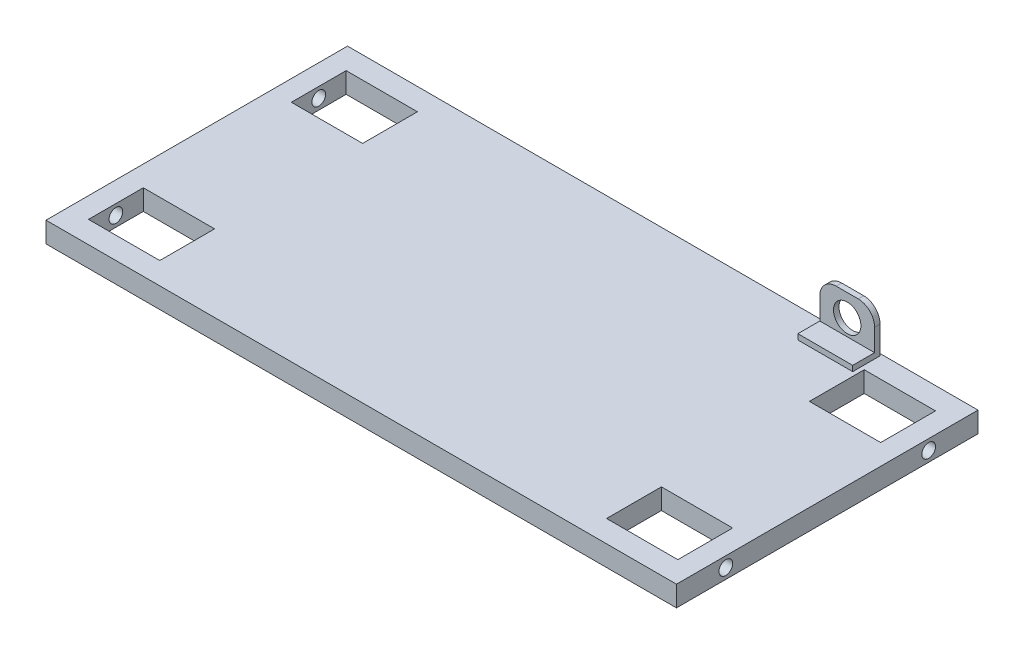
SolidWorks part; units mm, degrees
ref_plane "前视基准面" through (0, 0, 0) normal (0, 0, 1) x (1, 0, 0)
ref_plane "上视基准面" through (0, 0, 0) normal (0, 1, 0) x (1, 0, 0)
ref_plane "右视基准面" through (0, 0, 0) normal (1, 0, 0) x (0, 0, -1)
sketch "Sketch1" plane through (0, 0, 0) normal (0, 1, 0) x (1, 0, 0)
  line L1 (146.05, -69.85) -> (-146.05, -69.85)
  line L2 (146.05, -69.85) -> (146.05, 69.85)
  line L3 (146.05, 69.85) -> (-146.05, 69.85)
  line L4 (-146.05, -69.85) -> (-146.05, 69.85)
  line L5 (146.05, -69.85) -> (-146.05, 69.85) construction
  line L6 (146.05, 69.85) -> (-146.05, -69.85) construction
  point P1 (0, 0)
  dimension "D1" = 139.7
  dimension "D2" = 292.1
extrude "Boss-Extrude1" add sketch "Sketch1" along normal blind 9.525
sketch "Sketch2" plane through (0, 9.525, 0) normal (0, 1, 0) x (1, 0, 0)
  line L0 (-146.05, 0) -> (146.05, 0) construction
  line L1 (-146.05, 69.85) -> (-146.05, -69.85) construction
  line L2 (146.05, -69.85) -> (146.05, 69.85) construction
  line L3 (0, 69.85) -> (0, -69.85) construction
  line L4 (146.05, 69.85) -> (-146.05, 69.85) construction
  line L5 (-146.05, -69.85) -> (146.05, -69.85) construction
  line L6 (-136.525, 34.29) -> (-103.505, 34.29)
  line L7 (-103.505, -59.69) -> (-136.525, -59.69)
  line L8 (-103.505, -59.69) -> (-103.505, -34.29)
  line L9 (-103.505, 59.69) -> (-136.525, 59.69)
  line L10 (-136.525, -59.69) -> (-136.525, -34.29)
  line L11 (-103.505, -59.69) -> (-136.525, 59.69) construction
  line L12 (-103.505, 59.69) -> (-136.525, -59.69) construction
  line L13 (-136.525, -34.29) -> (-103.505, -34.29)
  line L14 (-103.505, 34.29) -> (-103.505, 59.69)
  line L15 (-136.525, 34.29) -> (-136.525, 59.69)
  line L16 (103.505, 34.29) -> (103.505, 59.69)
  line L17 (136.525, 34.29) -> (103.505, 34.29)
  line L18 (136.525, 34.29) -> (136.525, 59.69)
  line L19 (103.505, 59.69) -> (136.525, 59.69)
  line L20 (103.505, -59.69) -> (136.525, -59.69)
  line L21 (103.505, -59.69) -> (103.505, -34.29)
  line L22 (136.525, -59.69) -> (136.525, -34.29)
  line L23 (136.525, -34.29) -> (103.505, -34.29)
  point P12 (-120.015, 0)
  dimension "D1" = 10.16
  dimension "D2" = 33.02
  dimension "D3" = 25.4
  dimension "D4" = 9.525
extrude "Cut-Extrude1" cut sketch "Sketch2" against normal up to surface (9.525 mm away) up to face at (0, 0, 0)
sketch "Sketch3" plane through (146.05, 0, 0) normal (1, 0, 0) x (0, 0, -1)
  line L0 (-69.85, 4.7625) -> (69.85, 4.7625) construction
  line L1 (-69.85, 9.525) -> (-69.85, 0) construction
  line L2 (69.85, 9.525) -> (69.85, 0) construction
  line L3 (0, 9.525) -> (0, 0) construction
  line L4 (-69.85, 9.525) -> (69.85, 9.525) construction
  circle A0 centre (-46.99, 4.7625) radius 3.175
  circle A1 centre (46.99, 4.7625) radius 3.175
  dimension "D1" = 6.35
  dimension "D2" = 22.86
extrude "Cut-Extrude2" cut sketch "Sketch3" against normal blind 9.525
ref_plane "Plane1" through (0, 0, 0) normal (1, 0, 0) x (0, 0, -1)
mirror "Mirror1" about plane through (0, 0, 0) normal (1, 0, 0) of "Cut-Extrude2"
sketch "Sketch4" plane through (0, 9.525, 0) normal (0, 1, 0) x (1, 0, 0)
  line L0 (146.05, -69.85) -> (146.05, 69.85) construction
  line L1 (76.2, 68.9407) -> (101.6, 68.9407)
  line L2 (76.2, 68.9407) -> (76.2, 56.2407)
  line L3 (76.2, 56.2407) -> (101.6, 56.2407)
  line L4 (101.6, 68.9407) -> (101.6, 56.2407)
  line L5 (146.05, 69.85) -> (-146.05, 69.85) construction
  point P4 (88.9, 68.9407)
  dimension "D1" = 25.4
  dimension "D2" = 57.15
  dimension "D3" = 12.7
  dimension "D4" = 0.9093
extrude "Boss-Extrude2" add sketch "Sketch4" along normal blind 20.32
sketch "Sketch5" plane through (0, 29.845, 0) normal (0, 1, 0) x (1, 0, 0)
  line L0 (76.2, 68.9407) -> (76.2, 56.2407) construction
  line L1 (76.2, 66.4007) -> (101.6, 66.4007)
  line L2 (76.2, 66.4007) -> (76.2, 56.2407)
  line L3 (76.2, 56.2407) -> (101.6, 56.2407)
  line L4 (101.6, 66.4007) -> (101.6, 56.2407)
  line L5 (101.6, 68.9407) -> (76.2, 68.9407) construction
  dimension "D1" = 2.54
extrude "Cut-Extrude3" cut sketch "Sketch5" against normal blind 17.78
sketch "Sketch6" plane through (0, 0, -68.9407) normal (0, 0, -1) x (-1, 0, 0)
  line L0 (-101.6, 29.845) -> (-76.2, 9.525) construction
  circle A0 centre (-88.9, 19.685) radius 6.35
  point P4 (-88.9, 19.685)
  dimension "D1" = 12.7
fillet "Fillet2" radius 7.62 2 edges at (76.2, 29.845, -67.6707) (101.6, 29.845, -67.6707)
extrude "Cut-Extrude4" cut sketch "Sketch6" against normal up to surface (2.54 mm away) contours A0 up to face at (88.9, 21.9044, -66.4007)
